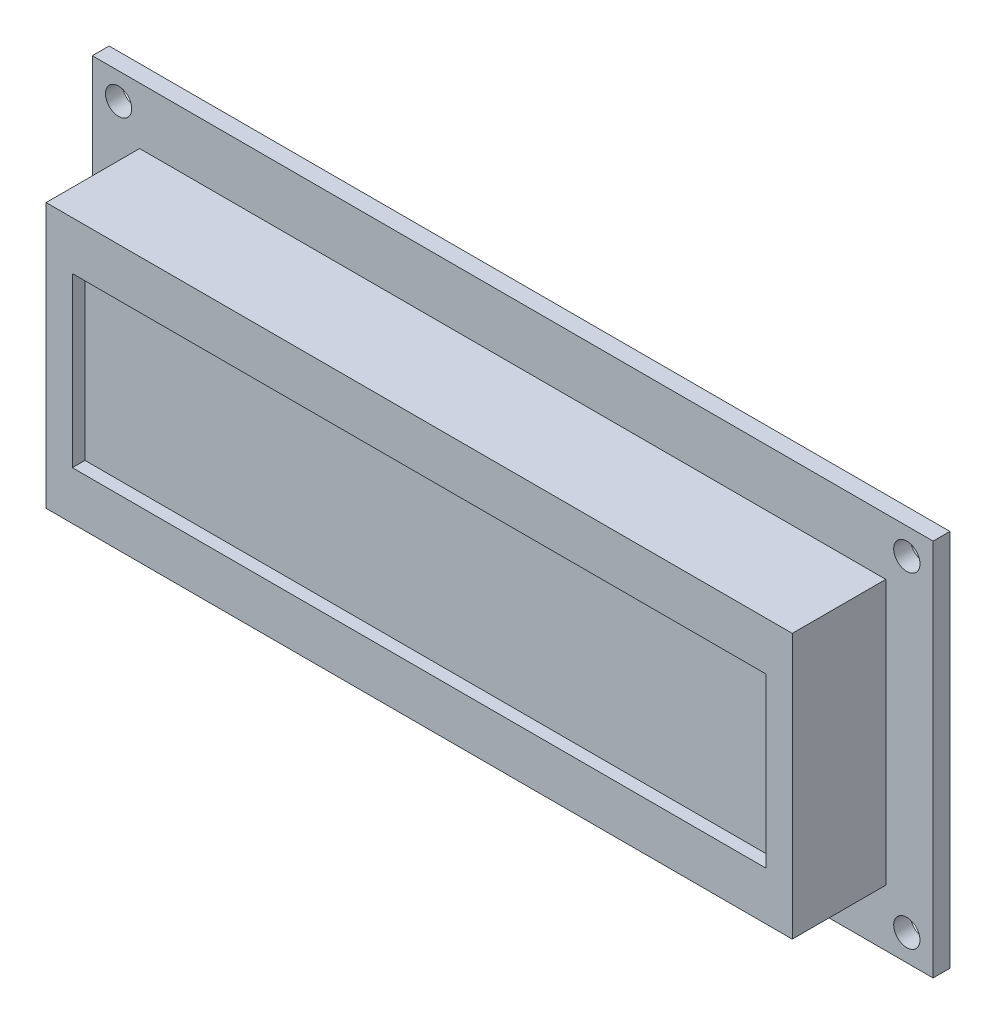
SolidWorks part; units mm, degrees
ref_plane "Front Plane" through (0, 0, 0) normal (0, 0, 1) x (1, 0, 0)
ref_plane "Top Plane" through (0, 0, 0) normal (0, 1, 0) x (1, 0, 0)
ref_plane "Right Plane" through (0, 0, 0) normal (1, 0, 0) x (0, 0, -1)
sketch "Sketch2" plane through (0, 0, 0) normal (0, 0, 1) x (1, 0, 0)
  line L1 (-40, 18) -> (40, 18)
  line L2 (-40, 18) -> (-40, -18)
  line L3 (-40, -18) -> (40, -18)
  line L4 (40, 18) -> (40, -18)
  line L5 (-40, 18) -> (40, -18) construction
  line L6 (-40, -18) -> (40, 18) construction
  line L7 (-35.5, 12.6) -> (35.5, 12.6)
  line L8 (-35.5, 12.6) -> (-35.5, -12.6)
  line L9 (-35.5, -12.6) -> (35.5, -12.6)
  line L10 (35.5, 12.6) -> (35.5, -12.6)
  line L11 (-35.5, 12.6) -> (35.5, -12.6) construction
  line L12 (-35.5, -12.6) -> (35.5, 12.6) construction
  line L13 (-33, 8) -> (33, 8)
  line L14 (-33, 8) -> (-33, -8)
  line L15 (-33, -8) -> (33, -8)
  line L16 (33, 8) -> (33, -8)
  line L17 (-33, 8) -> (33, -8) construction
  line L18 (-33, -8) -> (33, 8) construction
  point P0 (0, 0)
  point P5 (0, 0)
  point P11 (0, 0)
  dimension "D1" = 36
  dimension "D2" = 80
  dimension "D3" = 25.2
  dimension "D4" = 71
  dimension "D5" = 16
  dimension "D6" = 66
extrude "Boss-Extrude1" add sketch "Sketch2" against normal blind 1.6 contours L4 L1 L2 L3 L7 L10 L9 L8 | L10 L7 L8 L9 L13 L16 L15 L14 | L16 L13 L14 L15 region at (0, 17.1227, 0) region at (0, 11.8466, 0) region at (0, 0, 0)
extrude "Boss-Extrude2" add sketch "Sketch2<3>" against normal blind 13.5 from offset 8.9 contours L10 L7 L8 L9 L13 L16 L15 L14 | L16 L13 L14 L15 region at (0, 11.8466, 0) region at (0, 0, 0)
sketch "Sketch2<3>" plane through (0, 0, 0) normal (0, 0, 1) x (1, 0, 0) same geometry as "Sketch2"
extrude "Cut-Extrude1" cut sketch "Sketch2<4>" against normal blind 1.2 from surface contours L16 L13 L14 L15 region at (0, 0, 0) starting at face at (0, 0, 8.9)
sketch "Sketch2<4>" plane through (0, 0, 0) normal (0, 0, 1) x (1, 0, 0) same geometry as "Sketch2"
sketch "Sketch3" plane through (0, 0, 0) normal (0, 0, 1) x (1, 0, 0)
  line L0 (-40, 18) -> (40, 18) construction
  line L1 (40, 18) -> (40, -18) construction
  line L2 (0, -7.425) -> (0, 7.425) construction
  line L3 (7.425, 0) -> (-7.425, 0) construction
  circle A0 centre (37.5, 15.5) radius 1.25
  circle A1 centre (-37.5, 15.5) radius 1.25
  circle A2 centre (37.5, -15.5) radius 1.25
  circle A3 centre (-37.5, -15.5) radius 1.25
  dimension "D1" = 2.5
  dimension "D2" = 2.5
  dimension "D3" = 2.5
extrude "Cut-Extrude2" cut sketch "Sketch3" against normal through all
